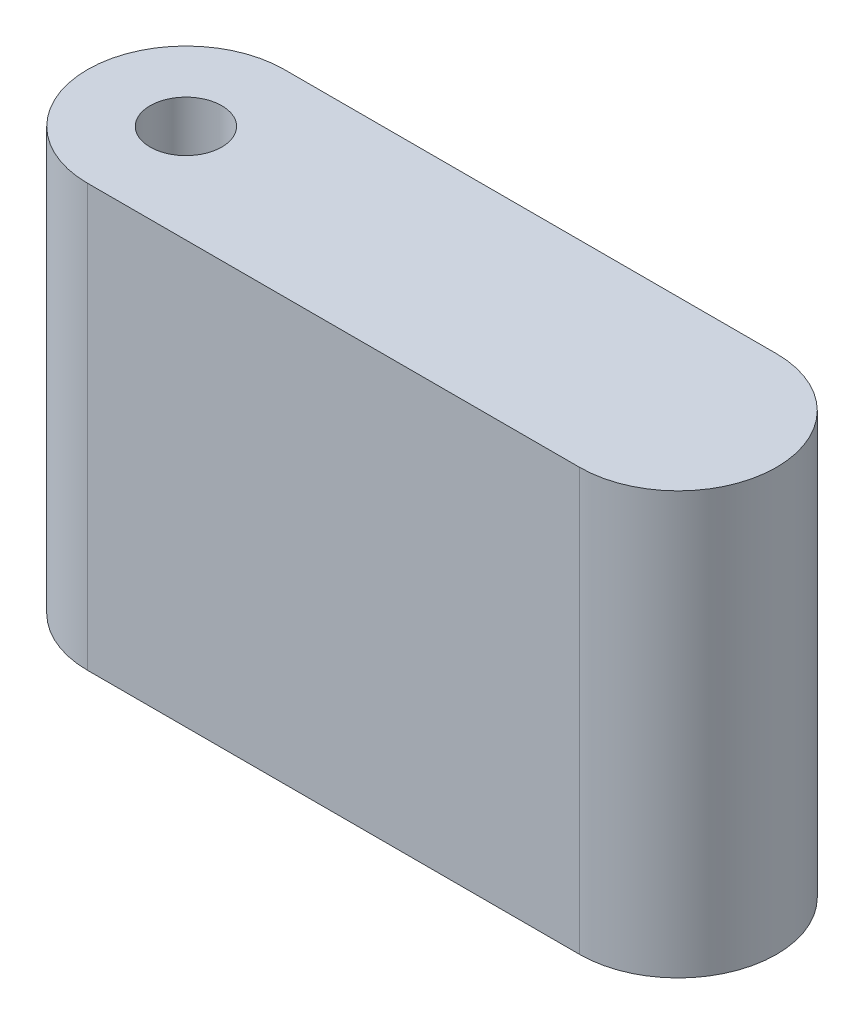
SolidWorks part; units mm, degrees
ref_plane "Ebene vorne" through (0, 0, 0) normal (0, 0, 1) x (1, 0, 0)
ref_plane "Ebene oben" through (0, 0, 0) normal (0, 1, 0) x (1, 0, 0)
ref_plane "Ebene rechts" through (0, 0, 0) normal (1, 0, 0) x (0, 0, -1)
sketch "Skizze1" plane through (0, 0, 0) normal (0, 1, 0) x (1, 0, 0)
  line L0 (0, 0) -> (35, 0) construction
  line L1 (0, 7) -> (35, 7)
  line L2 (0, -7) -> (35, -7)
  arc A0 (0, 7) -> (0, -7) centre (0, 0) ccw
  arc A1 (35, -7) -> (35, 7) centre (35, 0) ccw
  circle A2 centre (0, 0) radius 2.55
  point P3 (17.5, 0)
  dimension "D1" = 5.1
  dimension "D2" = 14
  dimension "D3" = 35
extrude "Aufsatz-Linear austragen1" add sketch "Skizze1" along normal blind 15 and the other way blind 15
ref_axis "Achse1" through (0, 16.5, 0) along (0, -1, 0)
